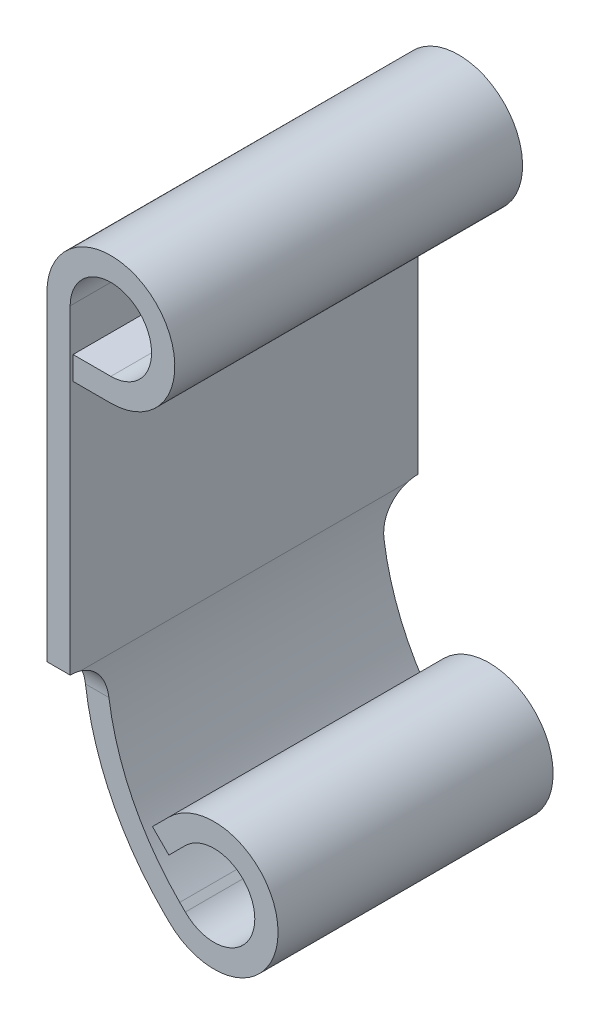
SolidWorks part; units mm, degrees
ref_plane "Ön Düzlem" through (0, 0, 0) normal (0, 0, 1) x (1, 0, 0)
ref_plane "Üst Düzlem" through (0, 0, 0) normal (0, 1, 0) x (1, 0, 0)
ref_plane "Sağ Düzlem" through (0, 0, 0) normal (1, 0, 0) x (0, 0, -1)
sketch "Çizim1" plane through (0, 0, 0) normal (0, 0, 1) x (1, 0, 0)
  line L2 (-3.3, -31.2819) -> (-4.7, -31.2819)
  line L3 (-4.7, -31.2819) -> (-5.5, -31.2819)
  line L4 (-2.464, -48.698) -> (-2.2716, -48.8904)
  line L5 (-5.1, -31.2819) -> (-5.1, -42.334)
  line L6 (-3.3, -33.0819) -> (-4.6, -33.0819)
  line L7 (-2.8373, -46.9105) -> (-2.2716, -46.3448)
  circle A1 centre (-3.3, -31.2819) radius 1.3 construction
  arc A2 (-3.3, -33.0819) -> (-5.1, -31.2819) centre (-3.3, -31.2819) ccw
  arc A3 (-2.2716, -48.8904) -> (-2.2716, -46.3448) centre (-0.9988, -47.6176) ccw
  arc A4 (-5.1, -42.334) -> (-2.464, -48.698) centre (3.9, -42.334) ccw
  point P18 (-5.1, -46.0619)
  dimension "D7" = 1.8
  dimension "D11" = 9
  dimension "D2" = 1.4
  dimension "D3" = 0.8
  dimension "D4" = 14.78
  dimension "D5" = 135
  dimension "D6" = 4
  dimension "D8" = 0.5
  dimension "D9" = 1.8
  dimension "D10" = 0.8
ref_plane "Düzlem1" through (-4.6, -33.0819, 0) normal (-1, 0, 0) x (0, 0, 1)
sketch "Çizim2" plane through (-4.6, -33.0819, 0) normal (-1, 0, 0) x (0, 0, 1)
  line L0 (0, 1.8) -> (0, -9.2521) construction
  line L1 (0, 1.8) -> (0, -9.2521) construction
  line L3 (-5.98, -0.4) -> (5.98, -0.4)
  line L4 (-5.98, -0.4) -> (-5.98, 0.4)
  line L5 (-5.98, 0.4) -> (5.98, 0.4)
  line L6 (5.98, -0.4) -> (5.98, 0.4)
  line L7 (-5.98, -0.4) -> (5.98, 0.4) construction
  line L8 (-5.98, 0.4) -> (5.98, -0.4) construction
  point P2 (0, 0)
  dimension "D1" = 0.8
  dimension "D2" = 11.96
sweep "Süpür1" add profiles "Çizim2" path "Çizim1"
sketch "Çizim3" plane through (-5.5, 0, 0) normal (-1, 0, 0) x (0, 0, 1)
  line L0 (-5.98, -42.334) -> (5.98, -42.334) construction
  line L1 (-5.98, -42.334) -> (5.98, -42.334) construction
  line L2 (-5.98, -31.2819) -> (5.98, -31.2819) construction
  line L3 (-5.98, -31.2819) -> (5.98, -31.2819) construction
  line L4 (0, -31.2819) -> (0, -42.2819) construction
  line L5 (-6.73, -42.2819) -> (6.73, -42.2819)
  line L7 (6.73, -52.2819) -> (6.73, -42.2819)
  line L8 (-6.73, -42.2819) -> (-6.73, -52.2819)
  line L9 (-6.73, -52.2819) -> (-4.73, -52.2819)
  line L10 (-4.73, -52.2819) -> (-4.73, -42.2819)
  line L12 (6.73, -52.2819) -> (4.73, -52.2819)
  line L13 (4.73, -52.2819) -> (4.73, -42.2819)
  line M2 (-5.98, -31.2819) -> (-5.98, -42.334)
  line M3 (-5.98, -42.334) -> (5.98, -42.334)
  line M4 (5.98, -42.334) -> (5.98, -31.2819)
  dimension "D1" = 11
  dimension "D2" = 4.73
  dimension "D3" = 4.73
  dimension "D4" = 10
  dimension "D5" = 10
  dimension "D6" = 2
  dimension "D7" = 2
extrude "Kes-Ekstrüzyon1" cut sketch "Çizim3" against normal blind 10 contours L13 L12 L7 L5 M4 M3 | L9 L10 L5 L8 M3 M2 | L13 L5 M3 M4 | L10 L5 M3 M2 region at (-5.5, -42.308, -5.355) region at (-5.5, -42.308, 5.355) region at (-5.5, -47.2982, -5.7312) region at (-5.5, -47.2982, 5.7312)
fillet "Radyus1" radius 1.25 2 edges at (-5.1, -42.2819, -4.73) (-5.1, -42.2819, 4.73)
